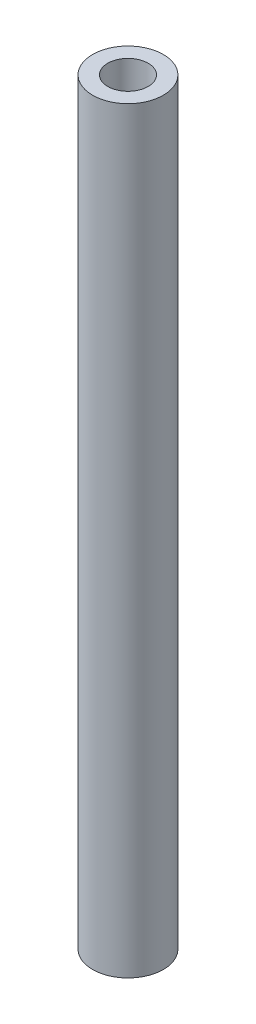
SolidWorks part; units mm, degrees
ref_plane "前视" through (0, 0, 0) normal (0, 0, 1) x (1, 0, 0)
ref_plane "上视" through (0, 0, 0) normal (0, 1, 0) x (1, 0, 0)
ref_plane "右视" through (0, 0, 0) normal (1, 0, 0) x (0, 0, -1)
sketch "草图1" plane through (0, 0, 0) normal (0, 1, 0) x (1, 0, 0)
  circle A0 centre (0, 0) radius 4
  circle A1 centre (0, 0) radius 7
  dimension "D1" = 8
  dimension "D2" = 14
extrude "凸台-拉伸1" add sketch "草图1" along normal blind 150
